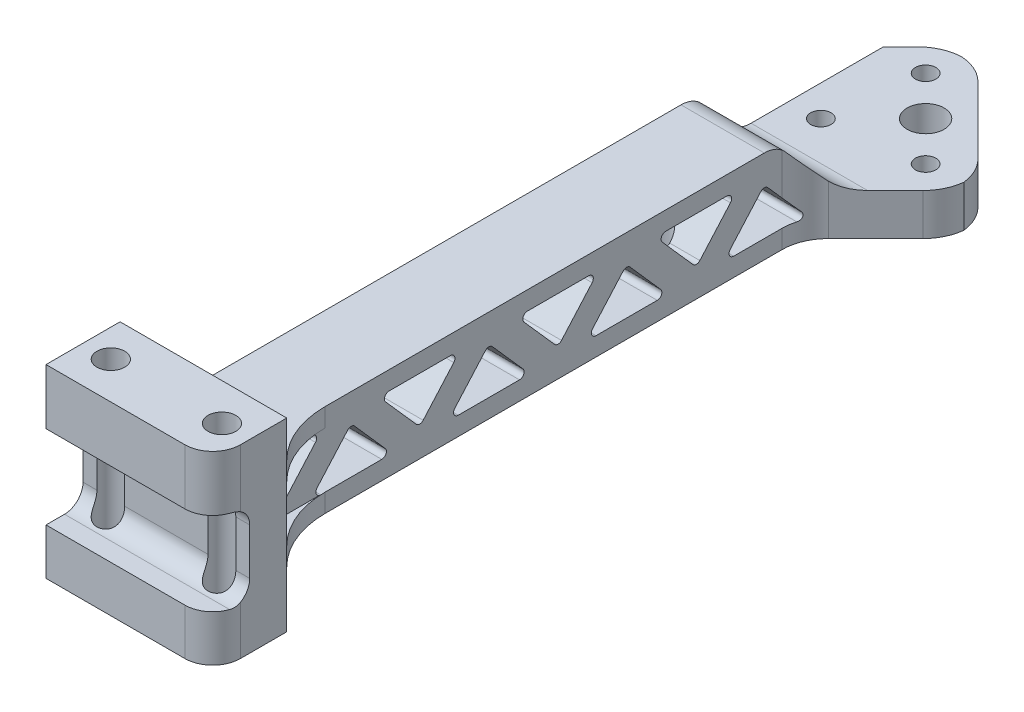
SolidWorks part; units mm, degrees
ref_plane "Front Plane" through (0, 0, 0) normal (0, 0, 1) x (1, 0, 0)
ref_plane "Top Plane" through (0, 0, 0) normal (0, 1, 0) x (1, 0, 0)
ref_plane "Right Plane" through (0, 0, 0) normal (1, 0, 0) x (0, 0, -1)
sketch "Sketch1" plane through (0, 0, 0) normal (0, 1, 0) x (1, 0, 0)
  line L0 (0, 90.435) -> (0, 0)
  line L1 (0, 0) -> (15, 0)
  line L2 (18, 3) -> (18, 8)
  line L3 (18, 8) -> (11.9289, 14.0711)
  line L4 (9, 21.1421) -> (9, 72.565)
  line L5 (9, 72.565) -> (9, 86) construction
  line L6 (3, 4) -> (15, 4) construction
  line L7 (0, 90.435) -> (3.3076, 93.7426)
  line L8 (3.3076, 93.7426) -> (6.9142, 93.7426)
  line L9 (6.9142, 93.7426) -> (17.0459, 83.6109)
  line L10 (17.0459, 83.6109) -> (17.0459, 80.6109)
  line L11 (17.0459, 80.6109) -> (9, 72.565)
  line L12 (9, 86) -> (13.2426, 81.7574) construction
  line L13 (3.3431, 80.3431) -> (9, 86) construction
  line L14 (9, 86) -> (4.7574, 90.2426) construction
  circle A0 centre (9, 86) radius 8 construction
  circle A1 centre (9, 86) radius 6 construction
  circle A2 centre (3, 4) radius 1.5
  circle A3 centre (15, 4) radius 1.5
  arc A4 (15, 0) -> (18, 3) centre (15, 3) ccw
  circle A5 centre (13.2426, 81.7574) radius 1.1
  circle A6 centre (3.3431, 80.3431) radius 1.1
  circle A7 centre (4.7574, 90.2426) radius 1.1
  arc A8 (11.9289, 14.0711) -> (9, 21.1421) centre (19, 21.1421) cw
  circle A9 centre (9, 86) radius 2
  point P19 (18, 0)
  dimension "D9" = 3
  dimension "D10" = 3
  dimension "D12" = 16
  dimension "D13" = 12
  dimension "D19" = 3.5
  dimension "D20" = 2.2
  dimension "D21" = 2.2
  dimension "D26" = 10
  dimension "D27" = 4
  dimension "D1" = 18
  dimension "D2" = 8
  dimension "D3" = 4
  dimension "D4" = 3
  dimension "D5" = 3
  dimension "D6" = 12
  dimension "D7" = 45
  dimension "D8" = 9
  dimension "D11" = 82
  dimension "D14" = 45
  dimension "D15" = 90
  dimension "D16" = 90
  dimension "D17" = 3.5
  dimension "D18" = 4.7574
  dimension "D22" = 3.5
  dimension "D23" = 45
  dimension "D24" = 4
  dimension "D25" = 3
extrude "Boss-Extrude2" add sketch "Sketch1" along normal blind 10
sketch "Sketch2" plane through (0, 0, 0) normal (-1, 0, 0) x (0, 0, 1)
  line L0 (-93.7426, 8) -> (2.3073, 8) construction
  line L1 (-93.7426, 10) -> (-93.7426, 0) construction
  line L2 (2.3073, 8) -> (2.3073, 7) construction
  line L3 (2.3073, 7) -> (-93.7426, 7) construction
  line L4 (-8, 8) -> (-8, 2)
  line L5 (-8, 2) -> (-13.3, 2)
  line L6 (2.3073, 6.0884) -> (2.3073, 5) construction
  line L7 (2.3073, 5) -> (-93.7426, 5) construction
  line L8 (-93.7426, 5) -> (-93.7426, 3) construction
  line L9 (-93.7426, 3) -> (2.3073, 3) construction
  line L10 (2.3073, 3) -> (2.3073, 2) construction
  line L11 (2.3073, 2) -> (-93.7426, 2) construction
  line L12 (-93.7426, 10) -> (-90.435, 10) construction
  line L13 (-93.7426, 0) -> (-90.435, 0) construction
  line L14 (-13.3, 2) -> (-8, 8)
  line L15 (-12.0028, 8) -> (-16.4195, 3)
  line L16 (-16.4195, 3) -> (-20.8361, 8)
  line L17 (-20.8361, 8) -> (-12.0028, 8)
  line L18 (-19.539, 2) -> (-23.9556, 7)
  line L19 (-23.9556, 7) -> (-28.3723, 2)
  line L20 (-28.3723, 2) -> (-19.539, 2)
  line L21 (-31.3602, 3) -> (-35.7769, 8)
  line L22 (-35.7769, 8) -> (-26.9436, 8)
  line L23 (-26.9436, 8) -> (-31.3602, 3)
  line L24 (-46.301, 3) -> (-50.7176, 8)
  line L25 (-50.7176, 8) -> (-41.8843, 8)
  line L26 (-41.8843, 8) -> (-46.301, 3)
  line L27 (-61.2417, 3) -> (-65.6584, 8)
  line L28 (-65.6584, 8) -> (-56.825, 8)
  line L29 (-56.825, 8) -> (-61.2417, 3)
  line L30 (-34.4139, 2) -> (-38.8306, 7)
  line L31 (-43.2473, 2) -> (-34.4139, 2)
  line L32 (-38.8306, 7) -> (-43.2473, 2)
  line L33 (-49.2889, 2) -> (-53.7056, 7)
  line L34 (-58.1222, 2) -> (-49.2889, 2)
  line L35 (-53.7056, 7) -> (-58.1222, 2)
  line L36 (-64.1639, 2) -> (-68.5805, 7)
  line L37 (-72.9972, 2) -> (-64.1639, 2)
  line L38 (-68.5805, 7) -> (-72.9972, 2)
  line L39 (-77, 8) -> (-77, 2)
  line L40 (-77, 2) -> (-71.7, 8)
  line L41 (-71.7, 8) -> (-77, 8)
  line L42 (0, 10) -> (0, 0) construction
  dimension "D1" = 2
  dimension "D2" = 2
  dimension "D3" = 1
  dimension "D4" = 1
  dimension "D5" = 2
  dimension "D6" = 3
  dimension "D7" = 5.3
  dimension "D8" = 3
  dimension "D9" = 3
  dimension "D12" = 8
  dimension "D13" = 77
  dimension "D14" = 3
  dimension "D10" = 4
  dimension "D11" = 4
extrude "Cut-Extrude1" cut sketch "Sketch2" against normal up to next
sketch "Sketch3" plane through (9, 0, 0) normal (1, 0, 0) x (0, 0, -1)
  line L1 (8, 8) -> (21.1421, 8)
  line L2 (8, 8) -> (8, 2)
  line L3 (8, 2) -> (21.1421, 2)
  line L4 (21.1421, 8) -> (21.1421, 2)
extrude "Cut-Extrude2" cut sketch "Sketch3" along normal blind 20
fillet "Fillet4" radius 0.5 29 edges at (4.5, 3, -46.301) (4.5, 8, -41.8843) (4.5, 2, -13.3) (9, 2, -8) (4.5, 8, -12.0028) (4.5, 8, -20.8361) (4.5, 7, -23.9556) (4.5, 8, -26.9436) (4.5, 7, -38.8306) (4.5, 8, -50.7176) (4.5, 8, -35.7769) (4.5, 2, -43.2473) (4.5, 2, -28.3723) (4.5, 3, -16.4195) (4.5, 3, -31.3602) (4.5, 2, -19.539) (4.5, 2, -34.4139) (4.5, 2, -49.2889) (4.5, 2, -58.1222) (4.5, 7, -53.7056) (4.5, 8, -56.825) (4.5, 8, -65.6584) (4.5, 3, -61.2417) (4.5, 2, -64.1639) (4.7161, 2, -72.9972) (4.5, 7, -68.5805) (4.5, 8, -71.7) (6.7175, 8, -77) (6.7175, 2, -77)
sketch "Sketch4" plane through (0, 10, 0) normal (0, 1, 0) x (1, 0, 0)
  line L0 (18, 8) -> (0, 8)
  line L1 (0, 8) -> (0, 0)
  line L2 (0, 0) -> (15, 0)
  line L3 (18, 3) -> (18, 8) construction
  line L4 (18, 3) -> (18, 8)
  arc A0 (15, 0) -> (18, 3) centre (15, 3) ccw construction
  arc A1 (15, 0) -> (18, 3) centre (15, 3) ccw
  circle A2 centre (15, 4) radius 1.5 construction
  circle A3 centre (3, 4) radius 1.5 construction
  circle A4 centre (15, 4) radius 1.5
  circle A5 centre (3, 4) radius 1.5
  dimension "D1" = 8
extrude "Boss-Extrude4" add sketch "Sketch4" along normal blind 10
sketch "Sketch5" plane through (0, 0, 0) normal (-1, 0, 0) x (0, 0, 1)
  line L0 (0, 20) -> (0, 0) construction
  line L1 (0, 14) -> (-4, 14)
  line L2 (0, 14) -> (0, 5)
  line L3 (0, 5) -> (-4, 5)
  line L4 (-4, 14) -> (-4, 5)
  line L5 (-90.435, 0) -> (0, 0) construction
  line L6 (-8, 20) -> (0, 20) construction
  dimension "D1" = 5
  dimension "D2" = 6
  dimension "D3" = 4
extrude "Cut-Extrude3" cut sketch "Sketch5" against normal through all
sketch "Sketch7" plane through (0, 0, 0) normal (-1, 0, 0) x (0, 0, 1)
  line L0 (-77, 7.5) -> (-77, 3.3213) construction
  line L1 (-76.1253, 2.9903) -> (-72.4341, 7.169) construction
  line L2 (-72.8088, 8) -> (-76.5, 8) construction
  line L3 (-77, 7.5) -> (-77, 3.3213)
  line L4 (-76.1253, 2.9903) -> (-72.4341, 7.169)
  line L5 (-72.8088, 8) -> (-76.5, 8)
  arc A0 (-77, 3.3213) -> (-76.1253, 2.9903) centre (-76.5, 3.3213) ccw construction
  arc A1 (-76.5, 8) -> (-77, 7.5) centre (-76.5, 7.5) ccw construction
  arc A2 (-72.4341, 7.169) -> (-72.8088, 8) centre (-72.8088, 7.5) ccw construction
  arc A3 (-77, 3.3213) -> (-76.1253, 2.9903) centre (-76.5, 3.3213) ccw
  arc A4 (-76.5, 8) -> (-77, 7.5) centre (-76.5, 7.5) ccw
  arc A5 (-72.4341, 7.169) -> (-72.8088, 8) centre (-72.8088, 7.5) ccw
extrude "Boss-Extrude11" add sketch "Sketch7" against normal up to surface (13.435 mm away) up to face at (11.9923, 5.8714, -75.5572)
sketch "Sketch8" plane through (0, 0, 0) normal (-1, 0, 0) x (0, 0, 1)
  line L0 (-69.9333, 10) -> (-74.7917, 4.5)
  line L1 (-90.435, 10) -> (-8, 10) construction
  line L2 (-74.7917, 4.5) -> (-93.7426, 4.5)
  line L3 (-93.7426, 10) -> (-93.7426, 0) construction
  line L4 (-93.7426, 4.5) -> (-93.7426, 10)
  line L5 (-93.7426, 10) -> (-69.9333, 10)
  line L6 (-68.9553, 6.5758) -> (-72.2631, 2.831) construction
  line L7 (-93.7426, 0) -> (-90.435, 0) construction
  point P13 (-92.0888, 0)
  dimension "D1" = 3
  dimension "D2" = 4.5
extrude "Cut-Extrude4" cut sketch "Sketch8" against normal through all
fillet "Fillet5" radius 2 2 edges at (9, 5, -4) (9, 14, -4)
sketch "Sketch12" plane through (0, 0, 0) normal (-1, 0, 0) x (0, 0, 1)
  line L0 (-8, 20) -> (-8, 10)
  line L1 (-8, 10) -> (-18, 10)
  line L2 (-69.9333, 10) -> (-8, 10) construction
  line L3 (-18, 10) -> (-8, 20)
  dimension "D1" = 45
extrude "Boss-Extrude12" add sketch "Sketch12" against normal blind 10
chamfer "Chamfer1" distance 7 angle 50 1 edges at (10, 15, -13) first distance on face at (10, 12.5, -12.6958)
fillet "Fillet6" radius 2 3 edges at (14, 10, -8) (5.8289, 15.0503, -8) (5.8289, 10, -13.0503)
fillet "Fillet7" radius 3 2 edges at (5.6133, 4.5, -74.7917) (4.5, 10, -69.9333)
fillet "Fillet8" radius 5 5 edges at (9, 3.5104, -72.565) (3.3076, 2.25, -93.7426) (6.9142, 2.25, -93.7426) (17.0459, 2.25, -83.6109) (17.0459, 2.25, -80.6109)
sketch "Sketch15" plane through (0, 0, 0) normal (0, -1, 0) x (1, 0, 0)
  line L0 (0, -90.435) -> (0, 0) construction
  circle A0 centre (4.5, -61.6355) radius 1.25
  point P6 (7.3413, -75.5623)
  point P9 (3.8723, -56.6113)
  dimension "D1" = 2.5
  dimension "D2" = 4.5
  dimension "D3" = 32.1
extrude "Cut-Extrude5" cut sketch "Sketch15" against normal blind 6
